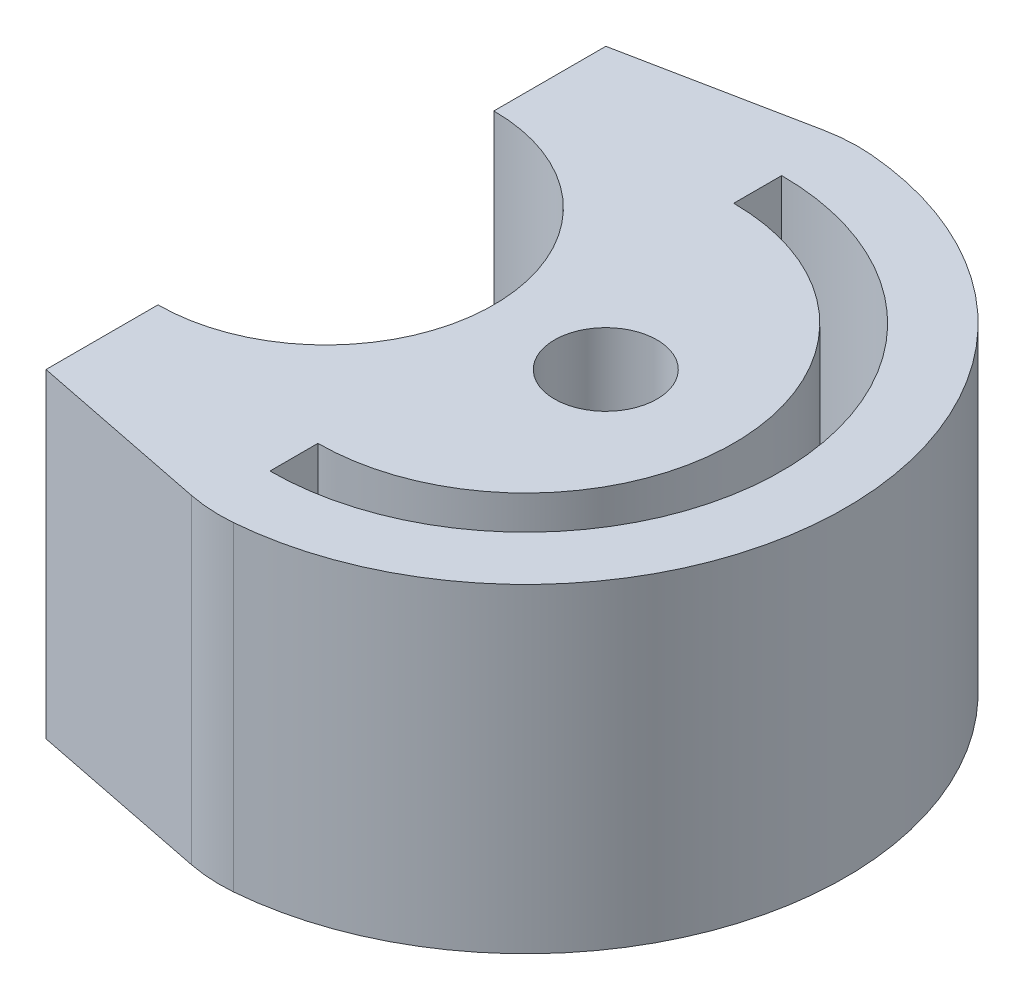
SolidWorks part; units mm, degrees
ref_plane "Front Plane" through (0, 0, 0) normal (0, 0, 1) x (1, 0, 0)
ref_plane "Top Plane" through (0, 0, 0) normal (0, 1, 0) x (1, 0, 0)
ref_plane "Right Plane" through (0, 0, 0) normal (1, 0, 0) x (0, 0, -1)
sketch "Sketch1" plane through (0, 0, 0) normal (0, 1, 0) x (1, 0, 0)
  line L0 (-0.1139, 1.9772) -> (-1.25, 1.7502)
  line L1 (-0.1139, -1.9772) -> (-1.25, -1.7502)
  line L2 (-1.25, 1.25) -> (-1.25, 1.7502)
  line L3 (-1.25, -1.25) -> (-1.25, -1.7502)
  line L4 (-1.25, -1.7502) -> (-4.1832, -1.1642)
  line L5 (-1.25, 1.7502) -> (-4.1832, 1.1642)
  line L6 (-1.25, 1.25) -> (-1.25, 1.05)
  line L7 (-1.25, -1.25) -> (-1.25, -1.05)
  line L8 (0, 1.6) -> (0, 1.3)
  line L9 (0, -1.3) -> (0, -1.6)
  line L17 (-4.25, 0.8) -> (-3.75, 0.8)
  line L18 (-4.25, 0.8) -> (-4.25, -0.8)
  line L19 (-4.25, -0.8) -> (-3.75, -0.8)
  line L20 (-3.75, 0.8) -> (-3.75, -0.8)
  circle A0 centre (-1.25, 0) radius 1.25
  circle A1 centre (-1.25, 0) radius 1.05
  arc A2 (0.1641, 1.9933) -> (0.1641, -1.9933) centre (0, 0) cw
  arc A3 (-0.1139, -1.9772) -> (0.1641, -1.9933) centre (0.0821, -0.9966) ccw
  arc A4 (-4.7783, 0.7954) -> (-4.7783, -0.7954) centre (-3.75, 0) ccw
  arc A5 (0.1641, 1.9933) -> (-0.1139, 1.9772) centre (0.0821, 0.9966) ccw
  arc A6 (-4.1832, 1.1642) -> (-4.7783, 0.7954) centre (-3.9873, 0.1835) ccw
  arc A7 (-4.1832, -1.1642) -> (-4.7783, -0.7954) centre (-3.9873, -0.1835) cw
  circle A8 centre (-3, 0) radius 0.3207
  circle A9 centre (0.5, 0) radius 0.3207
  arc A10 (0, 1.6) -> (0, -1.6) centre (0, 0) cw
  arc A11 (0, 1.3) -> (0, -1.3) centre (0, 0) cw
  point P12 (-3, 0)
  point P20 (0.5, 0)
extrude "Boss-Extrude1" add sketch "Sketch1" along normal blind 0.5 contours A2 A5 L0 L2 A0 L3 L1 A3 A9 region at (0.0275, 0, -1.9436)
extrude "Boss-Extrude2" add sketch "Sketch1<20>" along normal blind 1.5 from offset 0.5 contours A1 L7 A0 L6 | A2 A5 L0 L2 A0 L3 L1 A3 A9 region at (0.0275, 0, -1.9436) region at (-0.3859, 0, -0.8641)
sketch "Sketch1<20>" plane through (0, 0, 0) normal (0, 1, 0) x (1, 0, 0) same geometry as "Sketch1"
